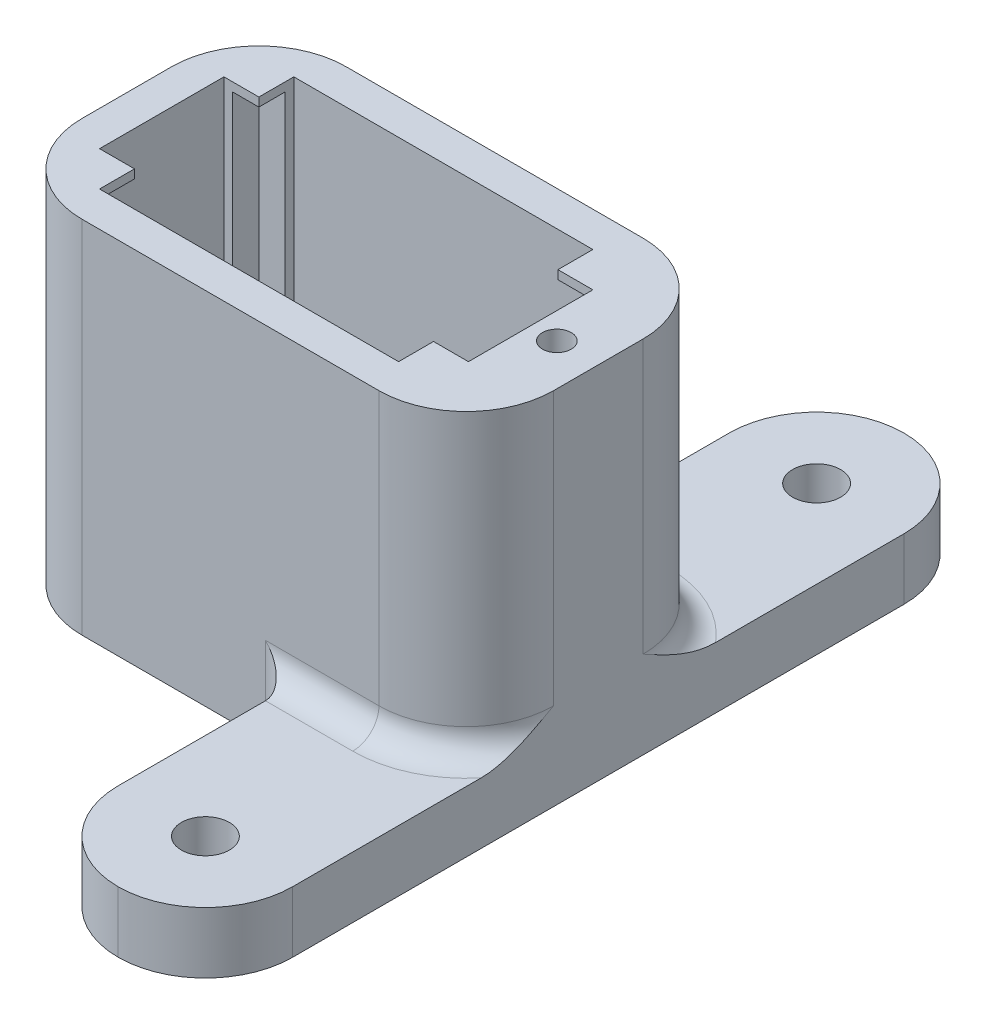
SolidWorks part; units mm, degrees
material "Nylon 101"
ref_plane "Front Plane" through (0, 0, 0) normal (0, 0, 1) x (1, 0, 0)
ref_plane "Top Plane" through (0, 0, 0) normal (0, 1, 0) x (1, 0, 0)
ref_plane "Right Plane" through (0, 0, 0) normal (1, 0, 0) x (0, 0, -1)
sketch "Sketch1" plane through (0, 20.13, 0) normal (0, 1, 0) x (1, 0, 0)
  line L0 (20.125, 10.125) -> (17.125, 10.125)
  line L1 (-20.125, 10.125) -> (-20.125, 7.125)
  line L2 (-20.125, -10.125) -> (-17.125, -10.125)
  line L3 (20.125, -10.125) -> (20.125, -7.125)
  line L4 (20.075, -10.075) -> (20.075, 10.075)
  line L5 (20.075, 10.075) -> (-20.075, 10.075)
  line L6 (-20.075, 10.075) -> (-20.075, -10.075)
  line L7 (-20.075, -10.075) -> (20.075, -10.075)
  line L10 (-20.075, 10.075) -> (-20.075, -10.075) construction
  line L12 (25.125, -15.125) -> (25.125, 15.125)
  line L13 (25.125, 15.125) -> (-25.125, 15.125)
  line L14 (-25.125, 15.125) -> (-25.125, -15.125)
  line L15 (-25.125, -15.125) -> (25.125, -15.125)
  line L16 (20.125, 7.125) -> (20.125, 10.125)
  line L17 (20.125, 7.125) -> (21.125, 7.125)
  line L19 (20.125, -7.125) -> (21.125, -7.125)
  line L20 (21.125, 7.125) -> (21.125, -7.125)
  line L21 (-20.125, 7.125) -> (-21.125, 7.125)
  line L23 (-20.125, -7.125) -> (-21.125, -7.125)
  line L24 (-21.125, 7.125) -> (-21.125, -7.125)
  line L26 (-17.125, 10.125) -> (-17.125, 11.125)
  line L27 (-17.125, 11.125) -> (17.125, 11.125)
  line L28 (17.125, 10.125) -> (17.125, 11.125)
  line L30 (17.125, -10.125) -> (17.125, -11.125)
  line L31 (17.125, -11.125) -> (-17.125, -11.125)
  line L32 (-17.125, -10.125) -> (-17.125, -11.125)
  line L33 (20.075, -10.075) -> (20.075, 10.075) construction
  line L34 (20.125, -10.125) -> (20.125, 10.125) construction
  line L35 (-20.075, -10.075) -> (20.075, -10.075) construction
  line L36 (17.125, -10.125) -> (20.125, -10.125)
  line L37 (-20.125, -10.125) -> (20.125, -10.125) construction
  line L38 (20.075, 10.075) -> (-20.075, 10.075) construction
  line L39 (-17.125, 10.125) -> (-20.125, 10.125)
  line L40 (20.125, 10.125) -> (-20.125, 10.125) construction
  line L41 (-20.125, -7.125) -> (-20.125, -10.125)
  line L42 (-20.125, 10.125) -> (-20.125, -10.125) construction
  dimension "D4" = 1
  dimension "D5" = 3
  dimension "D1" = 0
  dimension "D2" = 0.05
  dimension "D3" = 5
extrude "Boss-Extrude1" add sketch "Sketch1" against normal blind 19 and the other way blind 1
sketch "Sketch2" plane through (0, 0, 15.125) normal (0, 0, 1) x (1, 0, 0)
  line L0 (25.125, 21.13) -> (45.125, 21.13)
  line L1 (45.125, 21.13) -> (45.125, 61.13)
  line L2 (45.125, 61.13) -> (65.125, 61.13)
  line L3 (65.125, 61.13) -> (65.125, 1.13)
  line L4 (65.125, 1.13) -> (25.125, 1.13)
  line L5 (25.125, 1.13) -> (25.125, 21.13) construction
  line L6 (25.125, 21.13) -> (25.125, 1.13)
  dimension "D1" = 40
  dimension "D2" = 60
extrude "Boss-Extrude2" add sketch "Sketch2" against normal up to surface (30.25 mm away) up to face at (0, 11.13, -15.125)
sketch "Sketch3" plane through (0, 61.13, 0) normal (0, 1, 0) x (1, 0, 0)
  line L0 (55.125, 40) -> (55.125, -40) construction
  line L1 (65.125, 40) -> (65.125, -40)
  line L2 (45.125, 40) -> (45.125, -40)
  line L3 (45.125, -15.125) -> (65.125, 15.125) construction
  line L4 (65.125, 15.125) -> (65.125, -15.125) construction
  arc A0 (65.125, 40) -> (45.125, 40) centre (55.125, 40) ccw
  arc A1 (45.125, -40) -> (65.125, -40) centre (55.125, -40) ccw
  point P2 (55.125, 0)
  point P11 (55.125, 0)
  dimension "D1" = 80
extrude "Boss-Extrude3" add sketch "Sketch3" against normal blind 5
sketch "Sketch4" plane through (0, 56.13, 0) normal (0, -1, 0) x (1, 0, 0)
  circle A0 centre (55.125, 40) radius 3.35
  circle A1 centre (55.125, -40) radius 3.35
  dimension "D1" = 6.7
hole_wizard "M6 Clearance Hole1" positions "Sketch8" profile "Sketch9" hole size "M6" standard "ANSI Metric" end condition through all
sketch "Sketch8" plane through (0, 56.13, 0) normal (0, -1, 0) x (-1, 0, 0)
  point P0 (-55.125, -40)
  point P3 (-55.125, 40)
sketch "Sketch9" plane through (55.125, 56.13, 40) normal (1, 0, 0) x (0, 0, -1)
  line L0 (0, 0) -> (0, 5)
  line L1 (0, 5) -> (3.3, 5)
  line L2 (3.3, 5) -> (3.3, 0.025)
  line L3 (3.3, 0.025) -> (3.325, 0)
  line L5 (3.325, 0) -> (0, 0)
  line L6 (-3.3, 0.025) -> (-3.325, 0) construction
  line L11 (0, -6.35) -> (0, 107.95) construction
  dimension "Thru Hole Dia." = 6.6
  dimension "Thru Hole Depth" = 5
  dimension "Near C'Sink Dia." = 6.65
  dimension "Near C'Sink Angle" = 90
sketch "Sketch6" plane through (0, 21.13, 0) normal (0, 1, 0) x (1, 0, 0)
  line L0 (17.125, 11.125) -> (-17.125, 11.125) construction
  line L1 (21.125, 11.125) -> (17.125, 11.125)
  line L2 (21.125, 11.125) -> (21.125, 7.125)
  line L3 (21.125, 7.125) -> (17.125, 7.125)
  line L4 (17.125, 11.125) -> (17.125, 7.125)
  line L5 (21.125, -11.125) -> (17.125, -11.125)
  line L6 (21.125, -11.125) -> (21.125, -7.125)
  line L7 (21.125, -7.125) -> (17.125, -7.125)
  line L8 (17.125, -11.125) -> (17.125, -7.125)
  line L9 (-21.125, -11.125) -> (-17.125, -11.125)
  line L10 (-21.125, -11.125) -> (-21.125, -7.125)
  line L11 (-21.125, -7.125) -> (-17.125, -7.125)
  line L12 (-17.125, -11.125) -> (-17.125, -7.125)
  line L13 (-21.125, 11.125) -> (-17.125, 11.125)
  line L14 (-21.125, 11.125) -> (-21.125, 7.125)
  line L15 (-21.125, 7.125) -> (-17.125, 7.125)
  line L16 (-17.125, 11.125) -> (-17.125, 7.125)
  line L17 (21.125, -7.125) -> (21.125, 7.125) construction
  line L18 (-17.125, -11.125) -> (17.125, -11.125) construction
  line L19 (-21.125, 7.125) -> (-21.125, -7.125) construction
  line L20 (21.125, 7.125) -> (20.125, 7.125) construction
  line L21 (17.125, 10.125) -> (17.125, 11.125) construction
extrude "Boss-Extrude4" add sketch "Sketch6" against normal blind 1
fillet "Fillet1" radius 10 6 edges at (65.125, 1.13, 0) (55.125, 56.13, -15.125) (55.125, 56.13, 15.125) (45.125, 21.13, 0) (-25.125, 11.13, 15.125) (-25.125, 11.13, -15.125)
sketch "Sketch10" plane through (0, 1.13, 0) normal (0, -1, 0) x (1, 0, 0)
  line L1 (21.125, 7.125) -> (21.125, -7.125) construction
  line L2 (21.125, 0) -> (24.125, 0) construction
  circle A0 centre (24.125, 0) radius 2
  circle A1 centre (24.125, 0) radius 3.5
  dimension "D1" = 4
  dimension "D2" = 7
  dimension "D3" = 1
hole_wizard "Tap Drill for M4x0.7 Tap1" positions "Sketch11" profile "Sketch12" hole size "M4x0.7" standard "ANSI Metric" end condition through all
sketch "Sketch11" plane through (0, 1.13, 0) normal (0, -1, 0) x (-1, 0, 0)
  point P0 (-24.125, 0)
sketch "Sketch12" plane through (24.125, 1.13, 0) normal (1, 0, 0) x (0, 0, -1)
  line L0 (0, 0) -> (0, 60)
  line L1 (0, 60) -> (1.65, 60)
  line L2 (1.65, 60) -> (1.65, 0.025)
  line L3 (1.65, 0.025) -> (1.675, 0)
  line L5 (1.675, 0) -> (0, 0)
  line L6 (-1.65, 0.025) -> (-1.675, 0) construction
  line L11 (0, -6.35) -> (0, 107.95) construction
  dimension "Thru Hole Dia." = 3.3
  dimension "Thru Hole Depth" = 60
  dimension "Near C'Sink Dia." = 3.35
  dimension "Near C'Sink Angle" = 90
sketch "Sketch13" plane through (0, 21.13, 0) normal (0, 1, 0) x (1, 0, 0)
  line L0 (28.875, 5.125) -> (28.875, -5.125)
  line L1 (35.125, 15.125) -> (-15.125, 15.125) construction
  line L2 (-15.125, -15.125) -> (35.125, -15.125) construction
  line L3 (-25.125, 5.125) -> (-25.125, -5.125) construction
  line L4 (-15.125, -15.125) -> (18.875, -15.125)
  line L5 (-25.125, 5.125) -> (-25.125, -5.125)
  line L6 (18.875, 15.125) -> (-15.125, 15.125)
  arc A0 (-25.125, -5.125) -> (-15.125, -15.125) centre (-15.125, -5.125) ccw construction
  arc A1 (-15.125, 15.125) -> (-25.125, 5.125) centre (-15.125, 5.125) ccw construction
  arc A2 (-25.125, -5.125) -> (-15.125, -15.125) centre (-15.125, -5.125) ccw
  arc A3 (-15.125, 15.125) -> (-25.125, 5.125) centre (-15.125, 5.125) ccw
  arc A4 (28.875, -5.125) -> (18.875, -15.125) centre (18.875, -5.125) cw
  arc A5 (28.875, 5.125) -> (18.875, 15.125) centre (18.875, 5.125) ccw
  dimension "D1" = 10
  dimension "D2" = 54
extrude "Cut-Extrude1" cut sketch "Sketch13" against normal through all both and the other way through all flip side to cut
sketch "Sketch14" plane through (0, 1.13, 0) normal (0, -1, 0) x (1, 0, 0)
  line L0 (-21.125, 7.125) -> (-20.125, 7.125) construction
  line L1 (-20.125, 7.125) -> (-20.125, 10.125) construction
  line L2 (-20.125, 10.125) -> (-17.125, 10.125) construction
  line L3 (-17.125, 10.125) -> (-17.125, 11.125) construction
  line L4 (-17.125, 11.125) -> (17.125, 11.125) construction
  line L5 (17.125, 11.125) -> (17.125, 10.125) construction
  line L6 (17.125, 10.125) -> (20.125, 10.125) construction
  line L7 (20.125, 10.125) -> (20.125, 7.125) construction
  line L8 (20.125, 7.125) -> (21.125, 7.125) construction
  line L9 (21.125, 7.125) -> (21.125, -7.125) construction
  line L10 (21.125, -7.125) -> (20.125, -7.125) construction
  line L11 (20.125, -7.125) -> (20.125, -10.125) construction
  line L12 (20.125, -10.125) -> (17.125, -10.125) construction
  line L13 (17.125, -10.125) -> (17.125, -11.125) construction
  line L14 (-21.125, -7.125) -> (-21.125, 7.125) construction
  line L15 (-20.125, -7.125) -> (-21.125, -7.125) construction
  line L16 (-20.125, -10.125) -> (-20.125, -7.125) construction
  line L17 (-17.125, -10.125) -> (-20.125, -10.125) construction
  line L18 (-17.125, -11.125) -> (-17.125, -10.125) construction
  line L19 (17.125, -11.125) -> (-17.125, -11.125) construction
  line L20 (28.875, 5.125) -> (28.875, -5.125) construction
  line L21 (-15.125, 15.125) -> (18.875, 15.125) construction
  line L22 (-25.125, -5.125) -> (-25.125, 5.125) construction
  line L23 (18.875, -15.125) -> (-15.125, -15.125) construction
  line L24 (-21.125, 7.125) -> (-20.125, 7.125)
  line L25 (-20.125, 7.125) -> (-20.125, 10.125)
  line L26 (-20.125, 10.125) -> (-17.125, 10.125)
  line L27 (-17.125, 10.125) -> (-17.125, 11.125)
  line L28 (-17.125, 11.125) -> (17.125, 11.125)
  line L29 (17.125, 11.125) -> (17.125, 10.125)
  line L30 (17.125, 10.125) -> (20.125, 10.125)
  line L31 (20.125, 10.125) -> (20.125, 7.125)
  line L32 (20.125, 7.125) -> (21.125, 7.125)
  line L33 (21.125, 7.125) -> (21.125, -7.125)
  line L34 (21.125, -7.125) -> (20.125, -7.125)
  line L35 (20.125, -7.125) -> (20.125, -10.125)
  line L36 (20.125, -10.125) -> (17.125, -10.125)
  line L37 (17.125, -10.125) -> (17.125, -11.125)
  line L38 (-21.125, -7.125) -> (-21.125, 7.125)
  line L39 (-20.125, -7.125) -> (-21.125, -7.125)
  line L40 (-20.125, -10.125) -> (-20.125, -7.125)
  line L41 (-17.125, -10.125) -> (-20.125, -10.125)
  line L42 (-17.125, -11.125) -> (-17.125, -10.125)
  line L43 (17.125, -11.125) -> (-17.125, -11.125)
  line L44 (28.875, 5.125) -> (28.875, -5.125)
  line L45 (-15.125, 15.125) -> (18.875, 15.125)
  line L46 (-25.125, -5.125) -> (-25.125, 5.125)
  line L47 (18.875, -15.125) -> (-15.125, -15.125)
  arc A0 (28.875, 5.125) -> (18.875, 15.125) centre (18.875, 5.125) ccw construction
  arc A1 (-15.125, 15.125) -> (-25.125, 5.125) centre (-15.125, 5.125) ccw construction
  arc A2 (-25.125, -5.125) -> (-15.125, -15.125) centre (-15.125, -5.125) ccw construction
  arc A3 (18.875, -15.125) -> (28.875, -5.125) centre (18.875, -5.125) ccw construction
  arc A4 (28.875, 5.125) -> (18.875, 15.125) centre (18.875, 5.125) ccw
  arc A5 (-15.125, 15.125) -> (-25.125, 5.125) centre (-15.125, 5.125) ccw
  arc A6 (-25.125, -5.125) -> (-15.125, -15.125) centre (-15.125, -5.125) ccw
  arc A7 (18.875, -15.125) -> (28.875, -5.125) centre (18.875, -5.125) ccw
extrude "Boss-Extrude5" add sketch "Sketch14" along normal blind 21.26
sketch "Sketch15" plane through (0, 21.13, 0) normal (0, 1, 0) x (1, 0, 0)
  circle A0 centre (24.125, 0) radius 1.65 construction
  circle A1 centre (24.125, 0) radius 1.65
extrude "Cut-Extrude2" cut sketch "Sketch15" against normal through all both and the other way through all
sketch "Sketch16" plane through (28.875, 0, 13.75) normal (-1, 0, 0) x (0, 0, 1)
  line L0 (-18.875, 21.13) -> (-18.875, -20.13) construction
  line L1 (-28.875, -20.13) -> (-18.875, -20.13)
  line L2 (-28.875, -20.13) -> (-28.875, -13.13)
  line L3 (-28.875, -13.13) -> (-18.875, -13.13)
  line L4 (-18.875, -20.13) -> (-18.875, -13.13)
  point P0 (0, 0)
  dimension "D1" = 7
  dimension "D2" = 10
extrude "Boss-Extrude6" add sketch "Sketch16" along normal up to next
sketch "Sketch17" plane through (28.875, 0, 0) normal (-1, 0, 0) x (0, 0, 1)
  line L7 (-11.125, -20.13) -> (-5.125, -20.13)
  line L8 (5.125, -20.13) -> (-5.125, -20.13) construction
  line L9 (5.125, -20.13) -> (-5.125, -20.13)
  line L10 (-11.125, 21.13) -> (-11.125, -20.13) construction
  line L11 (-11.125, 21.13) -> (-11.125, -20.13)
  line L12 (-15.125, -20.13) -> (-15.125, 21.13) construction
  line L13 (0, -13.13) -> (-45, -13.13)
  line L14 (0, -13.13) -> (0, -20.13)
  line L15 (0, -20.13) -> (-45, -20.13)
  line L16 (-45, -13.13) -> (-45, -20.13)
  line L17 (-15.125, -20.13) -> (-15.125, 21.13)
  point P8 (0, -20.13)
  line M32 (-15.125, -20.13) -> (-15.125, -13.13)
  dimension "D1" = 45
  dimension "D2" = 7
extrude "Boss-Extrude7" add sketch "Sketch17" along normal blind 20 contours L16 L13 L15 M32
fillet "Fillet2" [suppressed] radius 10
fillet "Fillet3" [suppressed] radius 3
sketch "Sketch18" [suppressed] plane through (0, -20.7339, 0) normal (0, 1, 0) x (1, 0, 0)
  line L0 (39.375, 45) -> (38.875, 45) construction
  line L1 (39.375, 45) -> (38.875, 45)
  arc A0 (49.375, 35) -> (39.375, 45) centre (39.375, 35) ccw construction
  arc A1 (38.875, 45) -> (28.875, 35) centre (38.875, 35) ccw construction
  arc A2 (49.375, 35) -> (39.375, 45) centre (39.375, 35) ccw
  arc A3 (38.875, 45) -> (28.875, 35) centre (38.875, 35) ccw
  circle A4 centre (39.125, 35) radius 2.75
  point P8 (39.125, 45)
  dimension "D1" = 5.5
  dimension "D2" = 10
extrude "Cut-Extrude3" [suppressed] cut sketch "Sketch18" against normal through all and the other way through all contours A4
fillet "Fillet5" radius 10 2 edges at (8.875, -16.63, -45) (28.875, -16.63, -45)
fillet "Fillet6" radius 3 3 edges at (13.875, -13.13, -15.125) (8.875, -16.63, -15.125) (25.9461, -13.13, -12.1961)
sketch "Sketch19" plane through (0, -13.13, 0) normal (0, 1, 0) x (1, 0, 0)
  circle A0 centre (18.875, 35) radius 2.75
  arc A1 (28.875, 35) -> (18.875, 45) centre (18.875, 35) ccw construction
  arc A2 (18.875, 45) -> (8.875, 35) centre (18.875, 35) ccw construction
  arc A3 (28.875, 35) -> (18.875, 45) centre (18.875, 35) ccw
  arc A4 (18.875, 45) -> (8.875, 35) centre (18.875, 35) ccw
  dimension "D2" = 5.5
  dimension "D1" = 10
extrude "Cut-Extrude4" cut sketch "Sketch19" against normal through all contours A0 region at (18.875, -13.13, -35)
mirror "Mirror2" about plane through (0, 0, 0) normal (0, 0, 1) of "Boss-Extrude6"
mirror "Mirror4" about plane through (0, 0, 0) normal (0, 0, 1) of "Boss-Extrude7"
fillet "Fillet7" radius 3 3 edges at (13.875, -13.13, 15.125) (8.875, -16.63, 15.125) (25.9461, -13.13, 12.1961)
fillet "Fillet8" radius 10 2 edges at (8.875, -16.63, 45) (28.875, -16.63, 45)
mirror "Mirror8" about plane through (0, 0, 0) normal (0, 0, 1) of "Cut-Extrude4"
